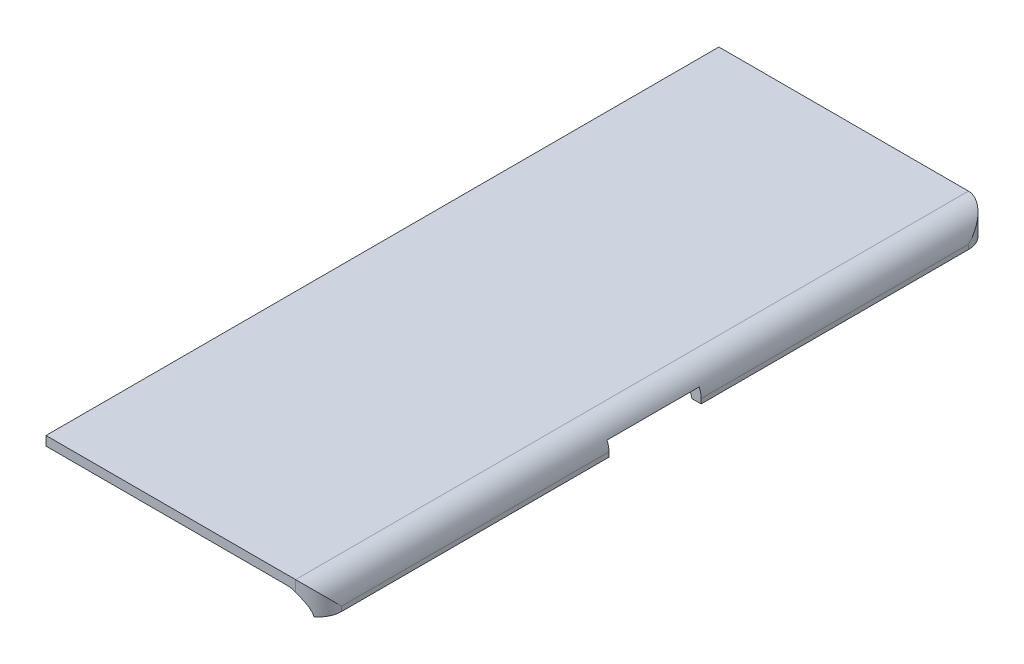
SolidWorks part; units mm, degrees
ref_plane "Front Plane" through (0, 0, 0) normal (0, 0, 1) x (1, 0, 0)
ref_plane "Top Plane" through (0, 0, 0) normal (0, 1, 0) x (1, 0, 0)
ref_plane "Right Plane" through (0, 0, 0) normal (1, 0, 0) x (0, 0, -1)
sketch "Sketch1" plane through (0, 0, 0) normal (0, 1, 0) x (1, 0, 0)
  line L1 (-57.15, 146) -> (0, 146)
  line L2 (-57.15, 146) -> (-57.15, 0)
  line L3 (-57.15, 0) -> (0, 0)
  line L4 (0, 146) -> (0, 0)
  dimension "D1" = 146
  dimension "D2" = 57.15
extrude "Boss-Extrude1" add sketch "Sketch1" along normal blind 2
sketch "Sketch2" plane through (0, 0, 0) normal (1, 0, 0) x (0, 0, -1)
  line L1 (0, 2) -> (146, 2)
  line L2 (0, 2) -> (0, -4)
  line L3 (0, -4) -> (146, -4)
  line L4 (146, 2) -> (146, -4)
  dimension "D1" = 6
  dimension "D2" = 146
extrude "Boss-Extrude2" add sketch "Sketch2" along normal blind 2
fillet "Fillet2" radius 5 2 edges at (2, -1, -146) (2, -1, 0)
fillet "Fillet4" radius 5 1 edges at (0, 0, -73)
sketch "Sketch3" plane through (2, 0, 0) normal (1, 0, 0) x (0, 0, -1)
  line L0 (73, 2) -> (73, -4)
  line L1 (141, 2) -> (5, 2) construction
  line L2 (5, -4) -> (141, -4) construction
  line L4 (83, -7) -> (63, -7)
  line L5 (83, -7) -> (83, -1)
  line L6 (83, -1) -> (63, -1)
  line L7 (63, -7) -> (63, -1)
  line L8 (83, -7) -> (63, -1) construction
  line L9 (83, -1) -> (63, -7) construction
  dimension "D1" = 20
  dimension "D2" = 6
extrude "Cut-Extrude1" cut sketch "Sketch3" against normal blind 10 contours L6 L7 L4 L5
fillet "Fillet5" radius 5 1 edges at (2, 2, -73)
